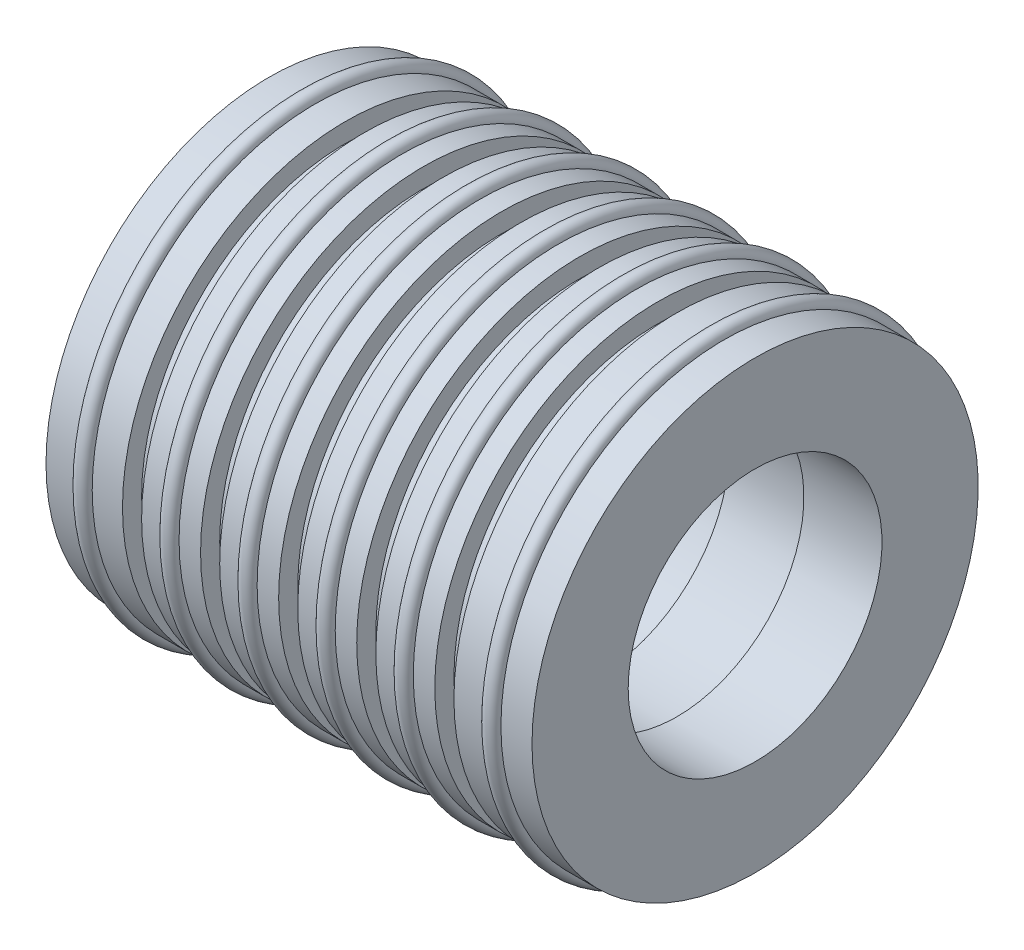
SolidWorks part; units mm, degrees
ref_plane "Front Plane" through (0, 0, 0) normal (0, 0, 1) x (1, 0, 0)
ref_plane "Top Plane" through (0, 0, 0) normal (0, 1, 0) x (1, 0, 0)
ref_plane "Right Plane" through (0, 0, 0) normal (1, 0, 0) x (0, 0, -1)
sketch "Sketch1" plane through (0, 0, 0) normal (0, 0, 1) x (1, 0, 0)
  line L0 (0, 0) -> (36.5459, 0) construction
  line L1 (-7.62, 11.3848) -> (-7.62, 17.78)
  line L3 (31.115, 17.78) -> (31.115, 10.1148)
  line L4 (31.115, 10.1148) -> (24.892, 10.1148)
  line L5 (24.892, 10.1148) -> (24.892, 10.3688)
  line L6 (24.892, 10.3688) -> (18.669, 10.3688)
  line L7 (18.669, 10.3688) -> (18.669, 10.6228)
  line L8 (18.669, 10.6228) -> (12.446, 10.6228)
  line L9 (12.446, 10.6228) -> (12.446, 10.8768)
  line L10 (12.446, 10.8768) -> (6.223, 10.8768)
  line L11 (6.223, 10.8768) -> (6.223, 11.1308)
  line L12 (6.223, 11.1308) -> (0, 11.1308)
  line L13 (0, 11.1308) -> (0, 11.3848)
  line L14 (0, 11.3848) -> (-7.62, 11.3848)
  line L15 (-7.62, 17.78) -> (-5.207, 17.78)
  line L16 (-1.524, 17.78) -> (-1.524, 16.256)
  line L17 (-1.524, 16.256) -> (0, 16.256)
  line L18 (0, 16.256) -> (0, 17.78)
  line L19 (0, 17.78) -> (1.7145, 17.78)
  line L20 (4.699, 17.78) -> (4.699, 16.256)
  line L21 (4.699, 16.256) -> (6.223, 16.256)
  line L22 (6.223, 16.256) -> (6.223, 17.78)
  line L23 (6.223, 17.78) -> (7.9375, 17.78)
  line L24 (10.922, 17.78) -> (10.922, 16.256)
  line L25 (10.922, 16.256) -> (12.446, 16.256)
  line L26 (12.446, 16.256) -> (12.446, 17.78)
  line L27 (12.446, 17.78) -> (14.1605, 17.78)
  line L28 (17.145, 17.78) -> (17.145, 16.256)
  line L29 (17.145, 16.256) -> (18.669, 16.256)
  line L30 (18.669, 16.256) -> (18.669, 17.78)
  line L31 (18.669, 17.78) -> (20.3835, 17.78)
  line L32 (23.368, 17.78) -> (23.368, 16.256)
  line L33 (23.368, 16.256) -> (24.892, 16.256)
  line L34 (24.892, 16.256) -> (24.892, 17.78)
  line L35 (24.892, 17.78) -> (27.3685, 17.78)
  line L36 (-3.937, 17.78) -> (-1.524, 17.78)
  line L37 (2.9845, 17.78) -> (4.699, 17.78)
  line L38 (9.2075, 17.78) -> (10.922, 17.78)
  line L39 (15.4305, 17.78) -> (17.145, 17.78)
  line L40 (21.6535, 17.78) -> (23.368, 17.78)
  line L41 (28.6385, 17.78) -> (31.115, 17.78)
  line L42 (-5.207, 17.78) -> (-3.937, 17.78) construction
  line L43 (1.7145, 17.78) -> (2.9845, 17.78) construction
  line L44 (7.9375, 17.78) -> (9.2075, 17.78) construction
  line L45 (14.1605, 17.78) -> (15.4305, 17.78) construction
  line L46 (20.3835, 17.78) -> (21.6535, 17.78) construction
  line L47 (27.3685, 17.78) -> (28.6385, 17.78) construction
  arc A9 (21.6535, 17.78) -> (20.3835, 17.78) centre (21.0185, 17.78) ccw
  arc A10 (15.4305, 17.78) -> (14.1605, 17.78) centre (14.7955, 17.78) ccw
  arc A11 (9.2075, 17.78) -> (7.9375, 17.78) centre (8.5725, 17.78) ccw
  arc A12 (2.9845, 17.78) -> (1.7145, 17.78) centre (2.3495, 17.78) ccw
  arc A13 (-3.937, 17.78) -> (-5.207, 17.78) centre (-4.572, 17.78) ccw
  arc A14 (28.6385, 17.78) -> (27.3685, 17.78) centre (28.0035, 17.78) ccw
  point P37 (-7.62, 14.5824)
  dimension "D13" = 1.27
  dimension "D1" = 10.1148
  dimension "D2" = 0.254
  dimension "D4" = 17.78
  dimension "D5" = 1.524
  dimension "D6" = 1.524
  dimension "D8" = 1.524
  dimension "D9" = 1.524
  dimension "D10" = 1.524
  dimension "D11" = 1.524
  dimension "D3" = 6.223
  dimension "D7" = 7.62
  dimension "D12" = 38.735
revolve "Revolve1" add sketch "Sketch1" angle 360 about L0
ref_plane "Plane1" through (-0.762, 0, 0) normal (-1, 0, 0) x (0, 0, 1)
ref_plane "Plane2" through (5.461, 0, 0) normal (-1, 0, 0) x (0, 0, 1)
ref_plane "Plane3" through (11.684, 0, 0) normal (1, 0, 0) x (0, 0, -1)
ref_plane "Plane4" through (17.907, 0, 0) normal (-1, 0, 0) x (0, 0, 1)
ref_plane "Plane5" through (24.13, 0, 0) normal (1, 0, 0) x (0, 0, -1)
ref_plane "Plane6" through (0, 17.78, 0) normal (0, 1, 0) x (1, 0, 0)
ref_axis "Axis1" through (0, 0, 0) along (-1, 0, 0)
sketch "Sketch4" plane through (-0.762, 0, 0) normal (-1, 0, 0) x (0, 0, 1)
  point P0 (0, 0)
sketch "Sketch5" plane through (5.461, 0, 0) normal (-1, 0, 0) x (0, 0, 1)
  point P0 (0, 0)
sketch "Sketch6" plane through (11.684, 0, 0) normal (1, 0, 0) x (0, 0, -1)
  point P0 (0, 0)
sketch "Sketch7" plane through (17.907, 0, 0) normal (-1, 0, 0) x (0, 0, 1)
  point P0 (0, 0)
sketch "Sketch8" plane through (24.13, 0, 0) normal (1, 0, 0) x (0, 0, -1)
  point P0 (0, 0)
sketch "Sketch9" plane through (0, 17.78, 0) normal (0, 1, 0) x (1, 0, 0)
  point P0 (24.13, 0)
  point P2 (17.907, 0)
  point P4 (11.684, 0)
  point P6 (5.461, 0)
  point P11 (-0.762, 0)
hole_wizard "#65 (0.035) Diameter Hole1" positions "Sketch9" profile "Sketch10" hole size "#65" standard "ANSI Inch" end condition up to next
sketch "Sketch10" plane through (24.13, 17.78, 0) normal (1, 0, 0) x (0, 0, 1)
  line L0 (0, 0) -> (0, 7.4112)
  line L1 (0, 7.4112) -> (0.4445, 7.4112)
  line L2 (0.4445, 7.4112) -> (0.4445, 0)
  line L5 (0.4445, 0) -> (0, 0)
  line L11 (0, -6.35) -> (0, 107.95) construction
  dimension "Thru Hole Dia." = 0.889
  dimension "Thru Hole Depth" = 7.4112
equation "\"kero_radius\"=0.23622in"
equation "\"lox_radius\"=0.23622in"
equation "\"Cavity_width\"=0.031in"
equation "\"tooth_width\"=0.01in"
equation "\"cavity_depth\"=0.031in"
equation "\"seal_step\"=0.01in"
equation "\"purge_length\"=0.04in"
equation "\"D1@Sketch1\"=\"lox_radius\"+\"seal_step\"+\"radial_clearance\"+.15"
equation "\"D2@Sketch1\"=\"seal_step\""
equation "\"insert_radius\" = 0.7in"
equation "\"recycle_groove width\" = 0.06in"
equation "\"D5@Sketch1\"=\"recycle_groove width\""
equation "\"recycle_groove_depth\" = 0.06in"
equation "\"D6@Sketch1\"=\"recycle_groove_depth\""
equation "\"N2_purge_width\"= .06in"
equation "\"N2_purge_depth\"= .06in"
equation "\"drain_width\"= .06in"
equation "\"drain_depth\"= .06in"
equation "\"D9@Sketch1\"=\"drain_depth\""
equation "\"D8@Sketch1\"=\"drain_width\""
equation "\"D10@Sketch1\"=\"N2_purge_depth\""
equation "\"D11@Sketch1\"=\"N2_purge_width\""
equation "\"radial_clearance\"= .002in"
equation "\"D3@Sketch1\"=\"tooth_width\"*5+\"Cavity_width\"*5+\"purge_length\""
equation "\"Insert_Length\"= \"D12@Sketch1\""
equation "\"InsertLength\"= 1.525in"
equation "\"D4@Sketch1\"=\"insert_radius\""
equation "\"bumb_radius\"= 0.05"
equation "\"D13@Sketch1\"=\"bumb_radius\""
